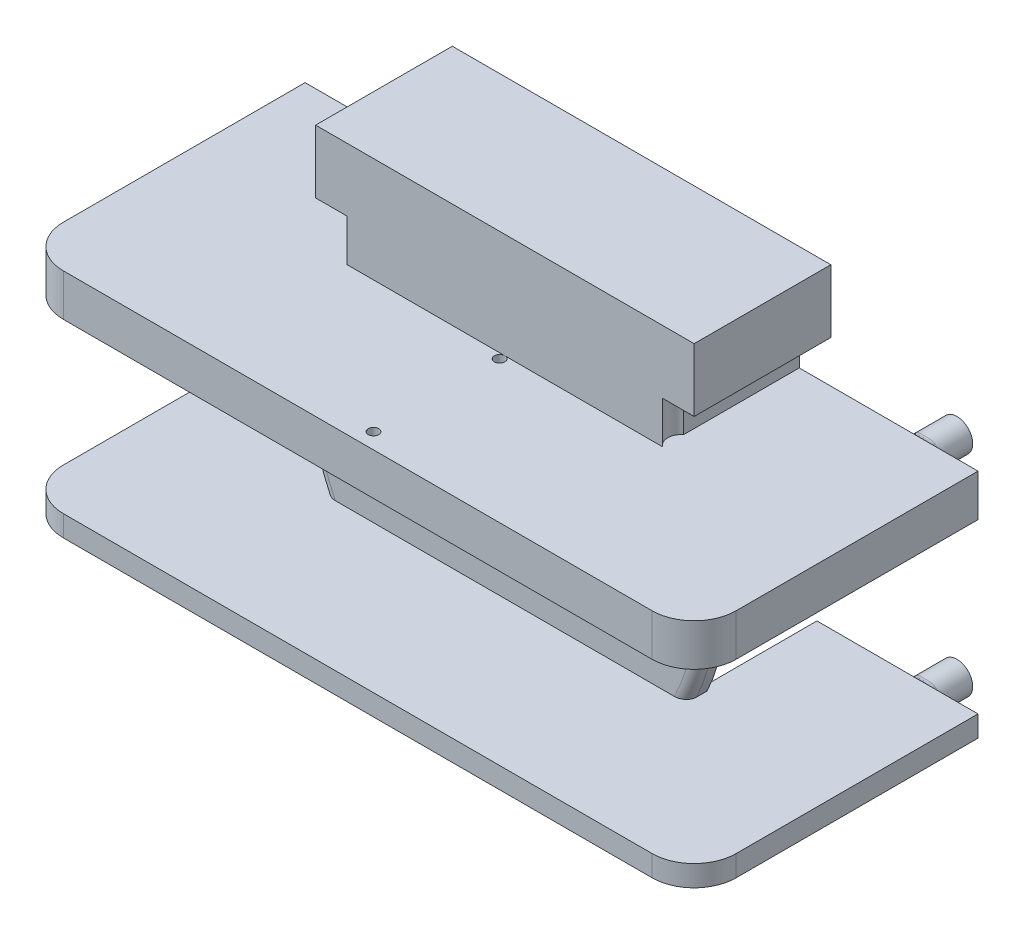
SolidWorks part; units mm, degrees
material "UNOBTANIUM"
ref_plane "Top Plane" through (0, 0, 0) normal (0, 0, 1) x (1, 0, 0)
ref_plane "Right Plane" through (0, 0, 0) normal (0, 1, 0) x (1, 0, 0)
ref_plane "Front Plane" through (0, 0, 0) normal (1, 0, 0) x (0, 0, -1)
ref_axis "x-axis" through (-17.6, 0, 0) along (1, 0, 0)
ref_axis "y-axis" through (0, -9.7375, 0) along (0, 1, 0)
ref_axis "z-axis" through (0, 0, 8.775) along (0, 0, -1)
sketch "Sketch1" plane through (0, 0, 0) normal (0, 0, 1) x (1, 0, 0)
  line L0 (-11, 6) -> (-11, 11)
  line L1 (-11, -6) -> (11, -6)
  line L2 (-11, -6) -> (-11, 6)
  line L3 (-11, 6) -> (11, 6) construction
  line L4 (11, -6) -> (11, 6)
  line L5 (-11, -6) -> (11, 6) construction
  line L6 (-11, 6) -> (11, -6) construction
  line L7 (-11, 11) -> (11, 11)
  line L8 (11, 11) -> (11, 6)
  circle A0 centre (0, 0) radius 8.75 construction
  point P0 (0, 0)
  dimension "D1" = 17.5
  dimension "D2" = 22
  dimension "D3" = 12
  dimension "D4" = 5
extrude "Boss-Extrude1" add sketch "Sketch1" along normal blind 1
sketch "Sketch2" plane through (0, 0, 0) normal (0, 0, -1) x (-1, 0, 0)
  circle A0 centre (0, 0) radius 1.5375
  dimension "D1" = 3.075
extrude "Boss-Extrude2" add sketch "Sketch2" along normal blind 4
sketch "Sketch3" plane through (0, 0, 0) normal (0, 0, -1) x (-1, 0, 0)
  line L0 (11, -6) -> (-11, 6) construction
  circle A0 centre (0, 0) radius 2
  dimension "D1" = 4
extrude "Boss-Extrude3" add sketch "Sketch3" along normal blind 0.5
sketch "Sketch4" plane through (0, 0, 0) normal (0, 0, -1) x (-1, 0, 0)
  line L0 (11, -6) -> (-11, -6) construction
  line L1 (11, 11) -> (9, 11)
  line L2 (11, 11) -> (11, -6)
  line L3 (11, -6) -> (9, -6)
  line L4 (9, 11) -> (9, -6)
  line L5 (0, -6) -> (0, 11) construction
  line L7 (-9, 11) -> (-9, -6)
  line L8 (-11, -6) -> (-9, -6)
  line L9 (-11, 11) -> (-11, -6)
  line L10 (-11, 11) -> (-9, 11)
  line L11 (11, 11) -> (-11, 11) construction
  dimension "D1" = 2
extrude "Boss-Extrude4" add sketch "Sketch4" along normal blind 5.5
sketch "Sketch5" plane through (0, 0, 0) normal (0, 0, -1) x (-1, 0, 0)
  line L0 (-9, -6) -> (-9, 11) construction
  line L1 (9, 11) -> (-9, 11)
  line L2 (9, 11) -> (9, 9)
  line L3 (9, 9) -> (-9, 9)
  line L4 (-9, 11) -> (-9, 9)
  dimension "D1" = 2
extrude "Boss-Extrude5" add sketch "Sketch5" along normal up to surface (5.5 mm away) up to face at (-10, 2.5, -5.5)
sketch "Sketch6" plane through (11, 0, 0) normal (1, 0, 0) x (0, 0, -1)
  line L0 (-1, -6) -> (-1, 11) construction
  line L1 (5.5, -6) -> (-1, -6)
  line L2 (5.5, -6) -> (5.5, -4)
  line L3 (5.5, -4) -> (-1, -4)
  line L4 (-1, -6) -> (-1, -4)
  line L6 (5.5, 11) -> (5.5, -6) construction
  line L7 (-1, 6) -> (5.5, 6)
  line L8 (-1, 6) -> (-1, 4)
  line L9 (-1, 4) -> (5.5, 4)
  line L10 (5.5, 6) -> (5.5, 4)
  line L11 (2.25, 4) -> (2.25, -4) construction
  line L12 (0, 0) -> (2.25, 0) construction
  line L13 (0, -6) -> (0, 6) construction
  point P21 (2.25, 0)
  dimension "D1" = 2
extrude "Boss-Extrude6" add sketch "Sketch6" along normal blind 5
mirror "Mirror1" about plane through (0, 0, 0) normal (1, 0, 0) of "Boss-Extrude6"
sketch "Sketch7" plane through (0, 0, -5.5) normal (0, 0, -1) x (-1, 0, 0)
  line L0 (-9, -6) -> (-9, 9) construction
  line L1 (-9, 0) -> (-9, 9)
  line L2 (-9, 9) -> (0, 9)
  line L3 (-9, 0) -> (-9, -6)
  line L4 (-9, -6) -> (-6.7082, -6)
  line L5 (11, -6) -> (-11, -6) construction
  arc A0 (0, 9) -> (-6.7082, -6) centre (0, 0) ccw
  line M18 (-9, -6) -> (-9, 9)
  line M19 (-9, 9) -> (9, 9)
extrude "Boss-Extrude7" add sketch "Sketch7" against normal up to surface (5.5 mm away) contours A0 L4 M18 | A0 M19 M18 region at (8.3306, -4.5409, -5.5) region at (6.9897, 6.9897, -5.5) up to face at (2, 0, 0)
sketch "Sketch8" plane through (0, 0, -5.5) normal (0, 0, -1) x (-1, 0, 0)
  line L0 (-11, 4) -> (-8.6168, 4)
  line L1 (-11, 4) -> (-11, -4)
  line L2 (-11, -4) -> (-8.6168, -4)
  arc A1 (-8.6168, 4) -> (-8.6168, -4) centre (0, 0) ccw
  dimension "D1" = 9.5
extrude "Cut-Extrude1" cut sketch "Sketch8" against normal through all
sketch "Sketch9" plane through (0, 0, -5.5) normal (0, 0, -1) x (-1, 0, 0)
  line L0 (-16, -4) -> (-8.6168, -4) construction
  line L1 (-8.0623, 4) -> (-11, 4)
  line L2 (-8.0623, 4) -> (-8.0623, -4)
  line L3 (-8.0623, -4) -> (-11, -4)
  line L4 (-11, 4) -> (-11, -4)
  line L5 (-11, -6) -> (-11, 6) construction
  arc A0 (0, 9) -> (-6.7082, -6) centre (0, 0) ccw construction
  arc A1 (0, 9) -> (-6.7082, -6) centre (0, 0) ccw construction
extrude "Cut-Extrude2" cut sketch "Sketch9" against normal up to surface (5.5 mm away) up to face at (2, 0, 0)
mirror "Mirror2" about plane through (0, 0, 0) normal (1, 0, 0) of "Cut-Extrude2", "Cut-Extrude1", "Boss-Extrude7"
sketch "Sketch21" plane through (0, 0, -5.5) normal (0, 0, -1) x (-1, 0, 0)
  circle A0 centre (0, 0) radius 9.25
  arc A1 (8.0623, 4) -> (-8.0623, 4) centre (0, 0) ccw construction
  circle A2 centre (0, 0) radius 2 construction
  circle A3 centre (0, 0) radius 2
  dimension "D1" = 0.25
extrude "Cut-Extrude11" cut sketch "Sketch21" against normal up to surface (5.5 mm away) up to face at (0, -0.7091, 0)
sketch "Sketch10" plane through (0, 0, 1) normal (0, 0, 1) x (1, 0, 0)
  line L0 (-16, -4) -> (-16, -6) construction
  line L1 (16, -6) -> (-16, -6)
  line L2 (16, -6) -> (16, -4)
  line L3 (16, -4) -> (-16, -4)
  line L4 (-16, -6) -> (-16, -4)
  line L5 (-16, -4) -> (-8.6168, -4) construction
  line L7 (-16, 6) -> (16, 6)
  line L8 (-16, 6) -> (-16, 4)
  line L9 (-16, 4) -> (16, 4)
  line L10 (16, 6) -> (16, 4)
extrude "Boss-Extrude8" add sketch "Sketch10" along normal blind 7
fillet "Fillet1" radius 0.5 2 edges at (9.5, 0, 1) (-9.5, 0, 1)
sketch "Sketch11" plane through (0, 0, -5.5) normal (0, 0, -1) x (-1, 0, 0)
  line L0 (-16, -5) -> (-13, -5) construction
  line L1 (-16, -6) -> (-16, -4) construction
  circle A0 centre (-13, -5) radius 0.75
  dimension "D1" = 1.5
  dimension "D2" = 3
extrude "Boss-Extrude9" add sketch "Sketch11" along normal blind 2
sketch "Sketch14" plane through (0, 0, -5.5) normal (0, 0, -1) x (-1, 0, 0)
  line L1 (11, 6) -> (7.5, 6)
  line L2 (11, 6) -> (11, 8)
  line L3 (11, 8) -> (7.5, 8)
  line L4 (7.5, 6) -> (7.5, 8)
  line L5 (-11, 6) -> (-7.5, 6)
  line L6 (-11, 6) -> (-11, 8)
  line L7 (-11, 8) -> (-7.5, 8)
  line L8 (-7.5, 6) -> (-7.5, 8)
  dimension "D1" = 15
  dimension "D2" = 2
extrude "Cut-Extrude5" cut sketch "Sketch14" against normal through all
sketch "Sketch12" plane through (0, 0, -5.5) normal (0, 0, -1) x (-1, 0, 0)
  line L0 (-16, -5) -> (-13, -5) construction
  line L1 (-16, -6) -> (-16, -4) construction
  line L3 (16, -5) -> (13, -5) construction
  line L4 (16, -6) -> (16, -4) construction
  circle A0 centre (13, -5) radius 0.8
  circle A1 centre (-13, -5) radius 0.75 construction
  circle A2 centre (-13, -5) radius 0.75 construction
  dimension "D1" = 1.6
  dimension "D2" = 1.5
extrude "Cut-Extrude3" cut sketch "Sketch12" against normal blind 2.5
sketch "Sketch16" plane through (0, 6, 0) normal (0, 1, 0) x (1, 0, 0)
  line L0 (-7.5, -1) -> (-7.5, 5.5) construction
  line L1 (-7.5, 0) -> (-7.5, -1)
  arc A1 (-7.5, 0) -> (-7.5, -1) centre (-7.875, -0.5) cw
  dimension "D1" = 0.25
  dimension "D2" = 1
extrude "Cut-Extrude6" cut sketch "Sketch16" along normal blind 2
mirror "Mirror3" about plane through (0, 0, 0) normal (0, 1, 0) of "Boss-Extrude9", "Cut-Extrude3"
mirror "Mirror4" about plane through (0, 0, 0) normal (1, 0, 0) of "Cut-Extrude6"
fillet "Fillet2" radius 0.5 2 edges at (12.25, 5, -5.5) (13.75, -5, -5.5)
fillet "Fillet3" radius 0.5 2 edges at (-13.8, 5, -5.5) (-13.8, -5, -5.5)
fillet "Fillet4" radius 2 4 edges at (16, -5, 8) (16, 5, 8) (-16, -5, 8) (-16, 5, 8)
sketch "Sketch17" plane through (0, -6, 0) normal (0, -1, 0) x (1, 0, 0)
  line L0 (-16, 6) -> (-16, -5.5) construction
  line L1 (-14, 8) -> (14, 8) construction
  line L2 (16, 6) -> (16, -5.5) construction
  line L3 (-16, 6) -> (-16, -5.5)
  line L4 (-14, 8) -> (14, 8)
  line L5 (16, 6) -> (16, -5.5)
  line L6 (14.5, 6) -> (14.5, -5.5)
  line L8 (-14, 6.5) -> (14, 6.5)
  line L9 (-14.5, 6) -> (-14.5, -5.5)
  line L10 (14.5, -5.5) -> (16, -5.5)
  line L11 (-14.5, -5.5) -> (-16, -5.5)
  arc A0 (-14, 8) -> (-16, 6) centre (-14, 6) ccw construction
  arc A1 (16, 6) -> (14, 8) centre (14, 6) ccw construction
  arc A2 (-14, 8) -> (-16, 6) centre (-14, 6) ccw
  arc A3 (16, 6) -> (14, 8) centre (14, 6) ccw
  arc A4 (14.5, 6) -> (14, 6.5) centre (14, 6) ccw
  arc A5 (-14, 6.5) -> (-14.5, 6) centre (-14, 6) ccw
  dimension "D1" = 1.5
extrude "Cut-Extrude7" cut sketch "Sketch17" against normal blind 1 and the other way through all
sketch "Sketch19" plane through (0, 6, 0) normal (0, 1, 0) x (1, 0, 0)
  line L0 (7.5, -1) -> (-7.5, -1) construction
  line L1 (0, -1.25) -> (0, -1) construction
  line L2 (7.5, -1) -> (-7.5, -1) construction
  circle A0 centre (0, -1.25) radius 0.25
  circle A1 centre (0, -7.25) radius 0.25
  point P4 (0, -1)
  dimension "D1" = 0.5
  dimension "D2" = 6
extrude "Cut-Extrude9" cut sketch "Sketch19" against normal up to surface (2 mm away) up to face at (-0.0216, 4, -0.5977)
sketch "Sketch20" plane through (0, 0, -5.5) normal (0, 0, -1) x (-1, 0, 0)
  line L0 (-7.5, 8) -> (-11, 8) construction
  line L1 (-11, 11) -> (-9, 11)
  line L2 (-11, 11) -> (-11, 8)
  line L3 (-11, 8) -> (-9, 8)
  line L4 (-9, 11) -> (-9, 8)
  line L5 (11, 11) -> (-11, 11) construction
  line L6 (11, 8) -> (9, 8)
  line L7 (11, 8) -> (11, 11)
  line L8 (11, 11) -> (9, 11)
  line L9 (9, 8) -> (9, 11)
  dimension "D1" = 2
extrude "Cut-Extrude10" cut sketch "Sketch20" against normal through all
equation "\"D1@Sketch12\"=\"D2@Sketch12\"+.1"
